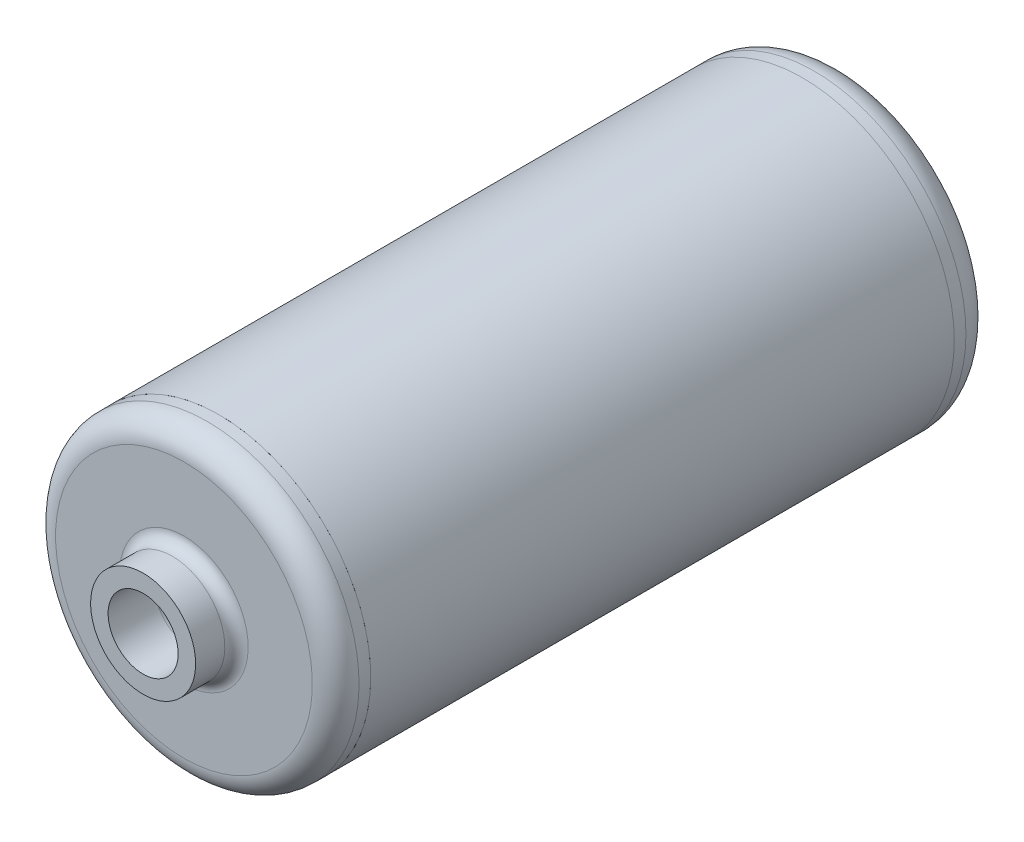
SolidWorks part; units mm, degrees
ref_plane "Alzado" through (0, 0, 0) normal (0, 0, 1) x (1, 0, 0)
ref_plane "Planta" through (0, 0, 0) normal (0, 1, 0) x (1, 0, 0)
ref_plane "Vista lateral" through (0, 0, 0) normal (1, 0, 0) x (0, 0, -1)
sketch "Croquis1" plane through (0, 0, 0) normal (0, 0, 1) x (1, 0, 0)
  circle A0 centre (0, 0) radius 26
  circle A1 centre (0, 0) radius 22
  dimension "D1" = 52
  dimension "D2" = 4
extrude "Saliente-Extruir1" add sketch "Croquis1" along normal blind 50 and the other way blind 50
ref_plane "Plano1" through (0, 0, 0) normal (1, 0, 0) x (0, 0, -1)
sketch "Croquis2" plane through (0, 0, 0) normal (1, 0, 0) x (0, 0, -1)
  line L0 (65.9873, 0) -> (-65.9873, 0) construction
  line L3 (-50, 26) -> (-50, -26) construction
  line L4 (-50, 26) -> (-50, -26) construction
  line L5 (50, -22) -> (50, 22) construction
  line L6 (50, -22) -> (50, 22) construction
  line L7 (-50, 22) -> (-50, -22) construction
  line L8 (-50, 22) -> (-50, -22) construction
  line L9 (-50, 22) -> (-43, 22)
  line L10 (-43, 22) -> (-43, 21)
  line L11 (-45, 19) -> (-49, 19)
  line L12 (-53, 15) -> (-53, 8)
  line L13 (-55, 6) -> (-63, 6)
  line L14 (-63, 6) -> (-63, 9)
  line L15 (-63, 9) -> (-58, 9)
  line L16 (-56, 11) -> (-56, 22)
  line L17 (-52, 26) -> (-50, 26)
  line L18 (-50, 26) -> (-50, 22)
  arc A0 (-56, 22) -> (-52, 26) centre (-52, 22) cw
  arc A1 (-49, 19) -> (-53, 15) centre (-49, 15) ccw
  arc A2 (-43, 21) -> (-45, 19) centre (-45, 21) cw
  arc A3 (-58, 9) -> (-56, 11) centre (-58, 11) ccw
  arc A4 (-53, 8) -> (-55, 6) centre (-55, 8) cw
  point P4 (0, 0)
  point P31 (0, 0)
  dimension "D8" = 4
  dimension "D9" = 2
  dimension "D1" = 6
  dimension "D2" = 3
  dimension "D3" = 3
  dimension "D4" = 3
  dimension "D5" = 10
  dimension "D6" = 3
  dimension "D7" = 10
revolve "Revolución2" add sketch "Croquis2" angle 360 about L0
sketch "Croquis3" plane through (0, 0, 0) normal (1, 0, 0) x (0, 0, -1)
  line L0 (0, 0) -> (78.2121, 0) construction
  line L1 (50, -22) -> (50, 22) construction
  line L2 (50, -22) -> (50, 22) construction
  line L3 (50, -26) -> (50, 26) construction
  line L4 (50, -26) -> (50, 26) construction
  line L5 (45, 22) -> (50, 22)
  line L6 (57, -26) -> (43, -26) construction
  line L7 (57, -26) -> (57, 26) construction
  line L8 (57, 26) -> (43, 26) construction
  line L9 (43, -26) -> (43, 26) construction
  line L10 (57, -26) -> (43, 26) construction
  line L11 (57, 26) -> (43, -26) construction
  line L12 (50, 22) -> (50, 26)
  line L13 (50, 26) -> (52, 26)
  line L14 (57, 21) -> (57, 8)
  line L15 (55, 6) -> (45, 6)
  line L16 (43, 8) -> (43, 20)
  arc A0 (52, 26) -> (57, 21) centre (52, 21) cw
  arc A1 (57, 8) -> (55, 6) centre (55, 8) cw
  arc A2 (45, 6) -> (43, 8) centre (45, 8) cw
  arc A3 (45, 22) -> (43, 20) centre (45, 20) ccw
  point P7 (50, 0)
  point P20 (57, 6)
  point P23 (43, 6)
  point P26 (43, 22)
  dimension "D3" = 5
  dimension "D4" = 2
  dimension "D1" = 14
  dimension "D2" = 6
revolve "Revolución3" add sketch "Croquis3" angle 360 about L0
